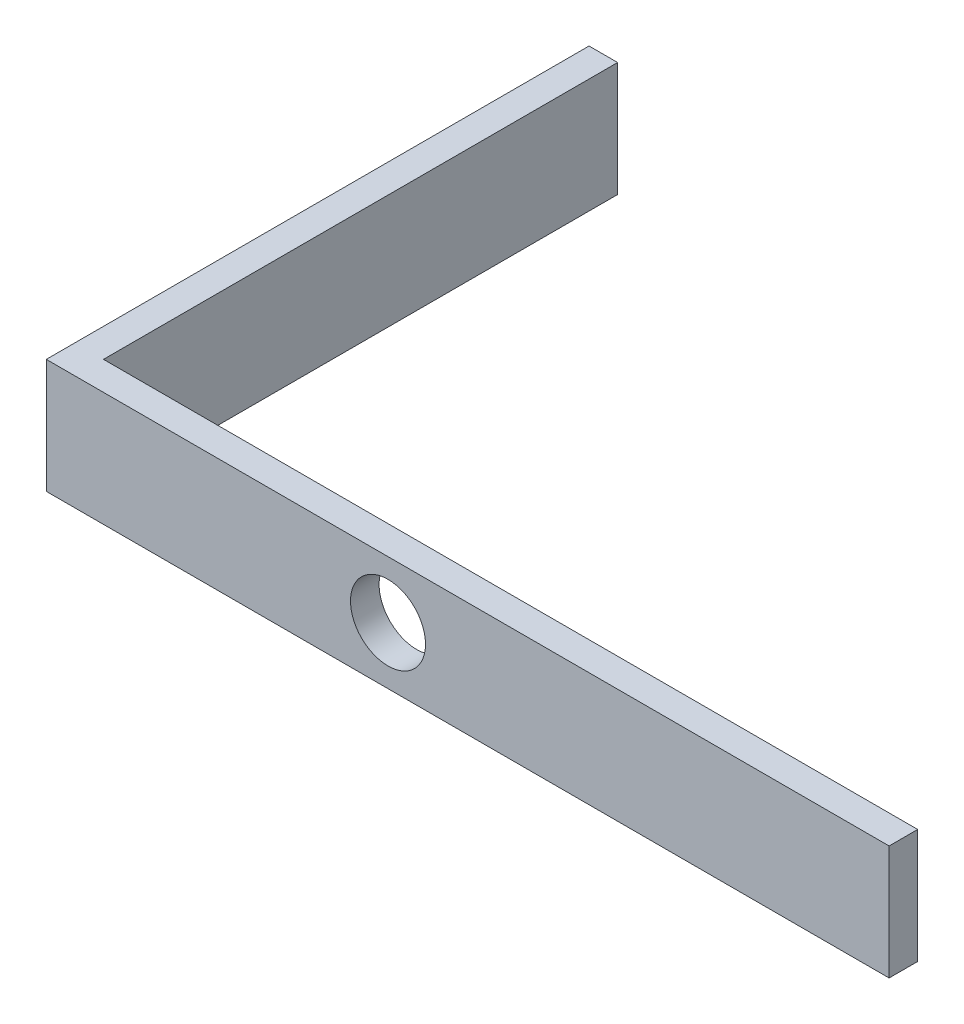
SolidWorks part; units mm, degrees
ref_plane "Front Plane" through (0, 0, 0) normal (0, 0, 1) x (1, 0, 0)
ref_plane "Top Plane" through (0, 0, 0) normal (0, 1, 0) x (1, 0, 0)
ref_plane "Right Plane" through (0, 0, 0) normal (1, 0, 0) x (0, 0, -1)
sketch "Sketch1" plane through (0, 0, 0) normal (0, 1, 0) x (1, 0, 0)
  line L1 (0, 0) -> (3.9688, 0)
  line L2 (0, 0) -> (0, 75.3427)
  line L3 (0, 75.3427) -> (3.9688, 75.3427)
  line L4 (3.9688, 3.9688) -> (3.9688, 75.3427)
  line L5 (3.9688, 0) -> (116.9988, 0)
  line L7 (3.9688, 3.9688) -> (116.9988, 3.9688)
  line L8 (116.9988, 0) -> (116.9988, 3.9688)
  dimension "D1" = 3.9688
  dimension "D2" = 3.9688
  dimension "D3" = 71.374
  dimension "D4" = 113.03
extrude "Boss-Extrude1" add sketch "Sketch1" along normal mid plane 15.875
sketch "Sketch2" plane through (0, 0, 0) normal (0, 0, 1) x (1, 0, 0)
  line L0 (0, 7.9375) -> (0, -7.9375) construction
  circle A0 centre (47.4345, 0) radius 5.207
  dimension "D1" = 47.4345
  dimension "D2" = 10.414
extrude "Cut-Extrude1" cut sketch "Sketch2" against normal up to surface (3.9688 mm away) up to face at (60.4838, 0, -3.9688)
